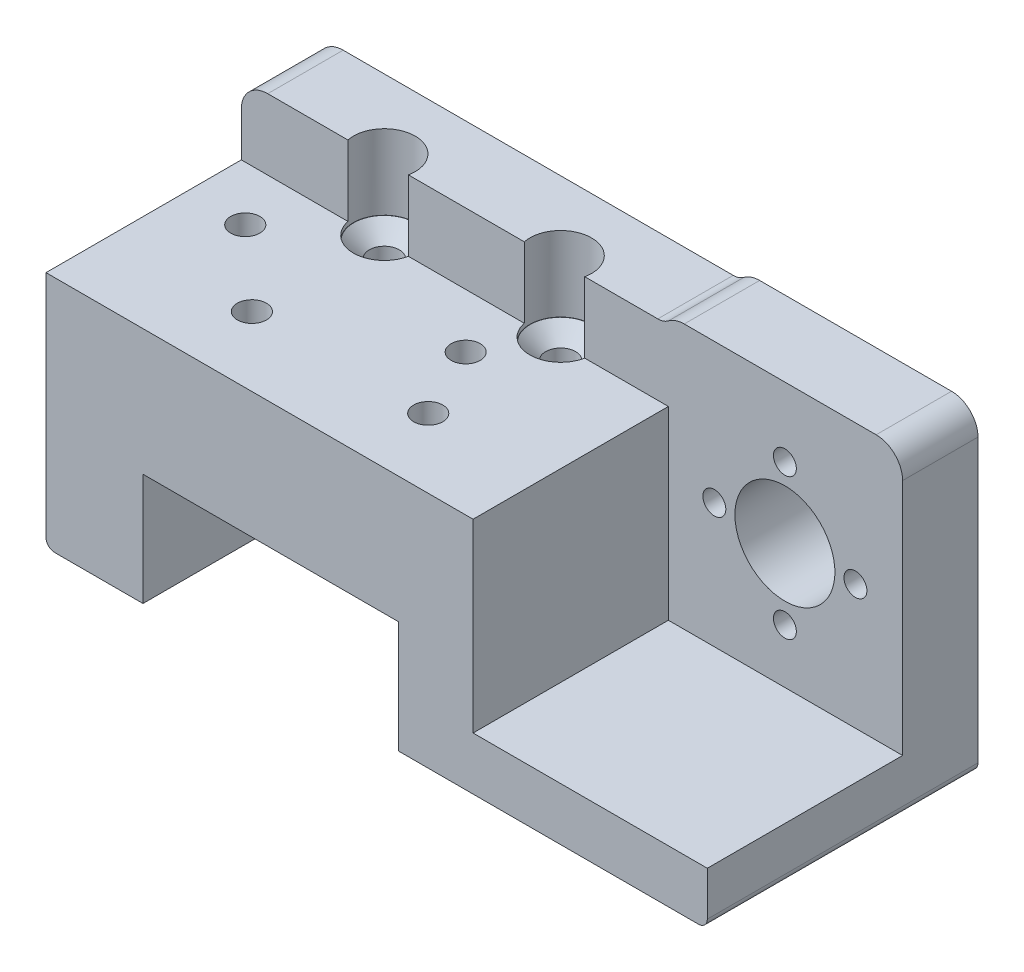
SolidWorks part; units mm, degrees
ref_plane "Front Plane" through (0, 0, 0) normal (0, 0, 1) x (1, 0, 0)
ref_plane "Top Plane" through (0, 0, 0) normal (0, 1, 0) x (1, 0, 0)
ref_plane "Right Plane" through (0, 0, 0) normal (1, 0, 0) x (0, 0, -1)
sketch "Croquis2" plane through (0, 0, 0) normal (0, 0, 1) x (1, 0, 0)
  line L0 (-42.15, -17.65) -> (-49.65, -17.65) construction
  line L1 (-42.15, -17.65) -> (-49.65, -17.65) construction
  line L2 (-49.65, -7.65) -> (-49.65, -17.65) construction
  line L3 (-49.65, -7.65) -> (-49.65, -17.65) construction
  line L5 (-61.65, -20.15) -> (13.35, -20.15)
  line L6 (-61.65, -20.15) -> (-61.65, 15.85)
  line L7 (-61.65, 15.85) -> (13.35, 15.85)
  line L8 (13.35, -20.15) -> (13.35, 15.85)
  line L9 (-50.65, -7.65) -> (-50.65, -7.45)
  line L10 (-21.65, -7.65) -> (-21.65, -17.65)
  line L11 (-21.65, -7.65) -> (-21.65, -20.15)
  line L13 (-50.65, -7.45) -> (-49.65, -7.45)
  line L14 (-21.65, -7.65) -> (-21.65, -7.45)
  line L15 (-21.65, -7.45) -> (-22.65, -7.45)
  line L16 (-50.65, -20.15) -> (-21.65, -20.15)
  line L17 (-30.45, -21.15) -> (-41.85, -21.15) construction
  line L18 (-49.65, -7.45) -> (-22.65, -7.45)
  line L19 (-49.65, -7.45) -> (-22.65, -7.45)
  line L28 (-50.65, -7.65) -> (-50.65, -17.65)
  line L29 (-50.65, -7.65) -> (-50.65, -20.15)
  circle A2 centre (0, 0) radius 5.67
  circle A3 centre (0, 0) radius 5.67
  circle A5 centre (0, 8) radius 1.3
  circle A6 centre (0, 8) radius 1.3
  circle A8 centre (8, 0) radius 1.3
  circle A9 centre (8, 0) radius 1.3
  circle A11 centre (0, -8) radius 1.3
  circle A12 centre (0, -8) radius 1.3
  circle A14 centre (-8, 0) radius 1.3
  circle A15 centre (-8, 0) radius 1.3
  circle M7 centre (0, 8) radius 1.6
  circle M8 centre (0, -8) radius 1.6
  circle M9 centre (8, 0) radius 1.6
  circle M10 centre (-8, 0) radius 1.6
  circle M12 centre (0, 0) radius 10.875
  dimension "D6" = 12
  dimension "D7" = 75
  dimension "D8" = 36
  dimension "D12" = 1
  dimension "D1" = 0.5
  dimension "D2" = 0.3
  dimension "D3" = 0.3
  dimension "D4" = 0.3
  dimension "D5" = 0.3
  dimension "D9" = 0.2
  dimension "D10" = 1
  dimension "D11" = 1
extrude "Saliente-Extruir1" add sketch "Croquis2" along normal offset from surface (30.7 mm away) 2 contours L29 L9 L13 L19 L15 L14 L11 L5 L8 L7 L6 M12 | A3 M12 M8 M10 M9 M7 | A6 M7 | A9 M9 | A12 M8 | A15 M10 region at (-26.4728, -0.3686, 0) region at (-1.5547, 8, 0) region at (-1.5547, -8, 0) region at (6.4453, 0, 0) region at (-9.5547, 0, 0) region at (-10.5674, 0, 0)
sketch "Croquis4" plane through (0, 0, 30.7) normal (0, 0, 1) x (1, 0, 0)
  line L0 (-61.65, 15.85) -> (13.35, 15.85) construction
  line L1 (-10.65, 15.85) -> (13.35, 15.85)
  line L2 (-10.65, 15.85) -> (-10.65, -14.15)
  line L3 (-10.65, -14.15) -> (13.35, -14.15)
  line L4 (13.35, 15.85) -> (13.35, -14.15)
  line L5 (13.35, -20.15) -> (13.35, 15.85) construction
  line M9 (13.35, -20.15) -> (13.35, 15.85)
  line M10 (13.35, 15.85) -> (-61.65, 15.85)
  circle M13 centre (0, 0) radius 5.67
  dimension "D1" = 24
  dimension "D2" = 30
extrude "Cortar-Extruir2" cut sketch "Croquis4" against normal offset from surface (22.7 mm away) 8 contours L2 L3 M9 M10 M13 region at (1.35, 15.4658, 30.7) up to face at (-30.15, -7.975, 0)
sketch "Croquis6" plane through (0, 0, 30.7) normal (0, 0, 1) x (1, 0, 0)
  line L0 (-30.15, -17.65) -> (-30.15, -13.15) construction
  line L1 (-21.65, -20.15) -> (-50.65, -20.15)
  line L2 (-21.65, -20.15) -> (-21.65, -7.45)
  line L3 (-21.65, -7.45) -> (-50.65, -7.45)
  line L4 (-50.65, -20.15) -> (-50.65, -7.45)
  line L5 (-30.15, -13.15) -> (-42.15, -13.15) construction
  line L6 (-42.15, -13.15) -> (-42.15, -17.65) construction
  line L7 (-29.65, -20.15) -> (-29.65, -12.65)
  line L8 (-29.65, -12.65) -> (-42.65, -12.65)
  line L9 (-42.65, -12.65) -> (-42.65, -20.15)
  line L10 (-29.65, -17.65) -> (-29.65, -12.65) construction
  line L11 (-42.65, -12.65) -> (-42.65, -17.65) construction
  dimension "D1" = 0.5
sketch "Croquis3" plane through (-61.65, 0, 0) normal (-1, 0, 0) x (0, 0, 1)
  line L0 (-2, -7.65) -> (32.7, -7.65) construction
  line L1 (20.85, 6.85) -> (8.55, 6.85)
  line L2 (20.85, 6.85) -> (20.85, 14.85)
  line L3 (20.85, 14.85) -> (8.55, 14.85)
  line L4 (8.55, 6.85) -> (8.55, 14.85)
  line L5 (0, -20.15) -> (0, 15.85) construction
  line L6 (30.7, 15.85) -> (30.7, -20.15) construction
  dimension "D1" = 8
  dimension "D2" = 12.3
  dimension "D3" = 14.5
  dimension "D4" = 9.85
  dimension "D5" = 8.55
extrude "Cortar-Extruir5" cut sketch "Croquis3" against normal through all
sketch "Croquis5" plane through (0, 15.85, 0) normal (0, 1, 0) x (1, 0, 0)
  line L2 (-61.65, -14.7) -> (-11.635, -14.7) construction
  line L4 (-61.65, -8.55) -> (-61.65, -20.85) construction
  line L5 (-61.65, -8.55) -> (-61.65, -20.85)
  circle A2 centre (-55.05, -14.7) radius 1.75 construction
  circle A3 centre (-55.05, -14.7) radius 1.75 construction
  circle A4 centre (-30.05, -14.7) radius 1.75 construction
  circle A5 centre (-30.05, -14.7) radius 1.75 construction
  circle A6 centre (-55.05, -14.7) radius 1.65
  circle A7 centre (-30.05, -14.7) radius 1.65
  point P11 (0, 0)
  point P13 (0, 0)
  point P14 (-27.175, -12.7653)
  point P15 (0, 0)
  dimension "D1" = 3.3
extrude "Cortar-Extruir6" cut sketch "Croquis5" against normal through all contours L2 | L2 | L2 | L2 | A6 | A7 region at (-55.05, 15.85, 14.7) region at (-30.05, 15.85, 14.7)
sketch "Croquis7" plane through (0, 15.85, 0) normal (0, 1, 0) x (1, 0, 0)
  line L0 (-61.65, 0) -> (13.35, 0) construction
  line L1 (-61.65, -30.7) -> (-10.65, -30.7)
  line L2 (-61.65, -30.7) -> (-61.65, 0)
  line L3 (-61.65, 0) -> (-10.65, 0)
  line L4 (-10.65, -30.7) -> (-10.65, 0)
  line L5 (-61.65, -8.55) -> (-61.65, -20.85) construction
  line L6 (-61.65, -8.55) -> (-61.65, -20.85)
  line L8 (-61.65, -20.85) -> (-10.65, -20.85)
  line L9 (-61.65, -20.85) -> (-61.65, -30.7)
  line L10 (-61.65, -30.7) -> (-10.65, -30.7)
  line L11 (-10.65, -20.85) -> (-10.65, -30.7)
  line M3 (-10.65, -30.7) -> (-10.65, -8)
  line M6 (13.35, 0) -> (-61.65, 0)
  line M7 (-61.65, 0) -> (-61.65, -30.7)
  line M8 (-61.65, -30.7) -> (-10.65, -30.7)
extrude "Cortar-Extruir7" cut sketch "Croquis7" against normal up to surface (1 mm away) contours L2 L8 L4 M6 M7 region at (-36.15, 15.85, 10.425) up to face at (-55.05, 14.85, 16.35)
sketch "Croquis9" plane through (-10.65, 0, 0) normal (-1, 0, 0) x (0, 0, 1)
  line L4 (8, 14.85) -> (8, 15.85)
  line L5 (8, 15.85) -> (0, 15.85)
  line L6 (0, 15.85) -> (0, 14.85)
  line L7 (0, 14.85) -> (8, 14.85)
  line L8 (8, 14.85) -> (8, 15.85)
  line L9 (8, 15.85) -> (0, 15.85)
  line L10 (0, 15.85) -> (0, 14.85)
  line L11 (0, 14.85) -> (8, 14.85)
  dimension "D1" = 0
extrude "Saliente-Extruir4" add sketch "Croquis9" along normal blind 3
extrude "Cortar-Extruir8" cut sketch "Croquis7<3>" against normal up to surface (9 mm away) contours L8 M7 M8 M3 region at (-36.15, 15.85, 25.775) up to face at (-55.05, 6.85, 13.05)
sketch "Croquis7<3>" plane through (0, 15.85, 0) normal (0, 1, 0) x (1, 0, 0) same geometry as "Croquis7"
sketch "Croquis11" plane through (0, 6.85, 0) normal (0, 1, 0) x (1, 0, 0)
  line L1 (-55.05, -11.2359) -> (-58.05, -12.9679)
  line L2 (-58.05, -12.9679) -> (-58.05, -16.4321)
  line L3 (-58.05, -16.4321) -> (-55.05, -18.1641)
  line L4 (-55.05, -18.1641) -> (-52.05, -16.4321)
  line L5 (-52.05, -16.4321) -> (-52.05, -12.9679)
  line L6 (-52.05, -12.9679) -> (-55.05, -11.2359)
  line L7 (-30.05, -11.2359) -> (-33.05, -12.9679)
  line L8 (-33.05, -12.9679) -> (-33.05, -16.4321)
  line L9 (-33.05, -16.4321) -> (-30.05, -18.1641)
  line L10 (-30.05, -18.1641) -> (-27.05, -16.4321)
  line L11 (-27.05, -16.4321) -> (-27.05, -12.9679)
  line L12 (-27.05, -12.9679) -> (-30.05, -11.2359)
  circle A0 centre (-46.1299, -7.85) radius 1.5 construction
  circle A1 centre (-26.1299, -7.85) radius 1.5 construction
  circle A2 centre (-26.15, -22.85) radius 1.5 construction
  circle A3 centre (-46.15, -22.85) radius 1.5 construction
  circle A4 centre (-46.1299, -7.85) radius 1.5 construction
  circle A5 centre (-26.1299, -7.85) radius 1.5 construction
  circle A6 centre (-26.15, -22.85) radius 1.5 construction
  circle A7 centre (-46.15, -22.85) radius 1.5 construction
  circle A8 centre (-46.1299, -7.85) radius 3.5
  circle A9 centre (-26.1299, -7.85) radius 3.5
  circle A10 centre (-26.15, -22.85) radius 3.5
  circle A11 centre (-46.15, -22.85) radius 3.5
  circle A12 centre (-55.05, -14.7) radius 3 construction
  circle A13 centre (-30.05, -14.7) radius 3 construction
  circle A14 centre (-46.1299, -7.85) radius 1.65
  circle A15 centre (-26.1299, -7.85) radius 1.65
  circle A16 centre (-26.15, -22.85) radius 1.65
  circle A17 centre (-46.15, -22.85) radius 1.65
  point P38 (-47.25, -14.7)
  point P39 (-45.1793, -14.8873)
  point P41 (0, 0)
  point P42 (0, 0)
  point P43 (0, 0)
  point P44 (0, 0)
  line M18 (-10.65, -8.55) -> (-61.65, -8.55)
  dimension "D1" = 7
  dimension "D2" = 6
  dimension "D3" = 3.3
extrude "Cortar-Extruir9" cut sketch "Croquis11" against normal offset from surface (8.5 mm away) 0.5 from surface contours A14 A8 M18 | A14 A8 L1 L6 M18 | A14 M18 | A14 M18 | A15 A9 M18 | A15 M18 | A15 M18 | A15 A9 M18 region at (-42.7288, 6.85, 8.1936) region at (-26.4734, 6.85, 4.4489) region at (-26.1299, 6.85, 9.849) region at (-46.1299, 6.85, 9.849) region at (-46.1299, 6.85, 8.9413) region at (-46.1299, 6.85, 7.5087) region at (-26.1299, 6.85, 8.9413) region at (-26.1299, 6.85, 7.5087) up to face at (-55.05, 6.85, 13.05) offset beyond the face yes starting at face at (-28.65, 14.85, 5.5167)
extrude "Cortar-Extruir10" cut sketch "Croquis11<3>" against normal through all contours A14 M18 | A14 M18 | A15 M18 | A15 M18 | A16 | A17 region at (-46.1299, 6.85, 8.9413) region at (-46.1299, 6.85, 7.5087) region at (-26.1299, 6.85, 8.9413) region at (-26.1299, 6.85, 7.5087) region at (-26.15, 6.85, 22.85) region at (-46.15, 6.85, 22.85)
sketch "Croquis11<3>" plane through (0, 6.85, 0) normal (0, 1, 0) x (1, 0, 0) same geometry as "Croquis11"
extrude "Cortar-Extruir11" cut sketch "Croquis11<4>" along normal blind 3 and the other way through all from surface contours L11 L12 L7 L8 L9 L10 | L1 A8 L6 region at (-55.05, 6.85, 14.7) region at (-30.05, 6.85, 14.7) starting at face at (-46.15, -7.45, 24.5)
sketch "Croquis11<4>" plane through (0, 6.85, 0) normal (0, 1, 0) x (1, 0, 0) same geometry as "Croquis11"
hole_wizard "Avellanado para tornillo con cabeza avellanada de clavija hexagonal de M31" positions "Croquis16" profile "Croquis17" countersink size "M3" standard "DIN" end condition through all
sketch "Croquis16" plane through (0, 6.35, 0) normal (0, 1, 0) x (1, 0, 0)
  point P0 (-46.1299, -7.85)
  point P3 (-26.1299, -7.85)
sketch "Croquis17" plane through (-46.1299, 6.35, 7.85) normal (1, 0, 0) x (0, 0, 1)
  line L0 (0, 0) -> (0, 26.5)
  line L1 (0, 26.5) -> (1.7, 26.5)
  line L2 (1.7, 26.5) -> (1.7, 1.77)
  line L3 (1.7, 1.77) -> (3.47, 0)
  line L5 (3.47, 0) -> (0, 0)
  line L6 (-1.7, 1.77) -> (-3.47, 0) construction
  line L11 (0, -6.35) -> (0, 107.95) construction
  dimension "Diámetro de taladro hasta el siguiente" = 3.4
  dimension "Profundidad de taladro hasta el siguiente" = 26.5
  dimension "Diámetro de avellanado cercano" = 6.94
  dimension "Ángulo de avellanado cercano" = 90
sketch "Croquis18" plane through (0, 6.85, 0) normal (0, 1, 0) x (1, 0, 0)
  line L0 (-10.65, -8.55) -> (-10.65, -30.7) construction
  line L1 (-61.65, -30.7) -> (-10.65, -30.7)
  line L2 (-61.65, -30.7) -> (-61.65, -27.2)
  line L3 (-61.65, -27.2) -> (-10.65, -27.2)
  line L4 (-10.65, -30.7) -> (-10.65, -27.2)
  dimension "D1" = 3.5
sketch "Croquis19" plane through (0, 0, 8) normal (0, 0, 1) x (1, 0, 0)
  line L4 (13.35, 15.85) -> (-13.65, 15.85)
  line L6 (-10.65, 14.85) -> (-10.65, -14.15)
  line L7 (-10.65, -14.15) -> (13.35, -14.15)
  line L8 (13.35, -14.15) -> (13.35, 15.85)
  line L12 (-10.65, 14.85) -> (-10.65, -14.15)
  line L13 (-10.65, -14.15) -> (13.35, -14.15)
  line L14 (13.35, -14.15) -> (13.35, 15.85)
  line L22 (13.35, 15.85) -> (-13.65, 15.85)
  line L23 (-13.65, 15.85) -> (-13.65, 14.85)
  line L24 (-13.65, 15.85) -> (-13.65, 14.85)
  line L25 (-13.65, 14.85) -> (-10.65, 14.85)
  line L26 (-13.65, 14.85) -> (-10.65, 14.85)
  circle A0 centre (0, 0) radius 5.67 construction
  circle A5 centre (0, 0) radius 5.67
  circle A10 centre (0, -8) radius 1.3 construction
  circle A11 centre (8, 0) radius 1.3 construction
  circle A12 centre (-8, 0) radius 1.3 construction
  circle A13 centre (0, 8) radius 1.3 construction
  circle A14 centre (0, -8) radius 1.3
  circle A15 centre (8, 0) radius 1.3
  circle A16 centre (-8, 0) radius 1.3
  circle A17 centre (0, 8) radius 1.3
  dimension "D1" = 0
extrude "Saliente-Extruir5" add sketch "Croquis19" along normal up to surface (0.55 mm away) up to face at (-16.6753, 10.85, 8.55)
fillet "Redondeo1" radius 3 2 edges at (13.35, 15.85, 4.275) (-13.65, 15.85, 4.275)
fillet "Redondeo2" radius 2 1 edges at (-13.65, 14.85, 4.275)
fillet "Redondeo3" radius 3 1 edges at (-61.65, 14.85, 4.275)
fillet "Redondeo4" radius 1 2 edges at (-61.65, -20.15, 15.35) (13.35, -20.15, 15.35)
sketch "Croquis20" plane through (-10.65, 0, 0) normal (1, 0, 0) x (0, 0, -1)
  line L4 (-8.55, -14.15) -> (-8.55, 6.85)
  line L5 (-8.55, 6.85) -> (-30.7, 6.85)
  line L6 (-30.7, 6.85) -> (-30.7, -14.15)
  line L7 (-30.7, -14.15) -> (-8.55, -14.15)
  line L8 (-8.55, -14.15) -> (-8.55, 6.85)
  line L9 (-8.55, 6.85) -> (-30.7, 6.85)
  line L10 (-30.7, 6.85) -> (-30.7, -14.15)
  line L11 (-30.7, -14.15) -> (-8.55, -14.15)
  dimension "D1" = 0
extrude "Cortar-Extruir12" cut sketch "Croquis20" against normal up to surface (2.5639 mm away)
